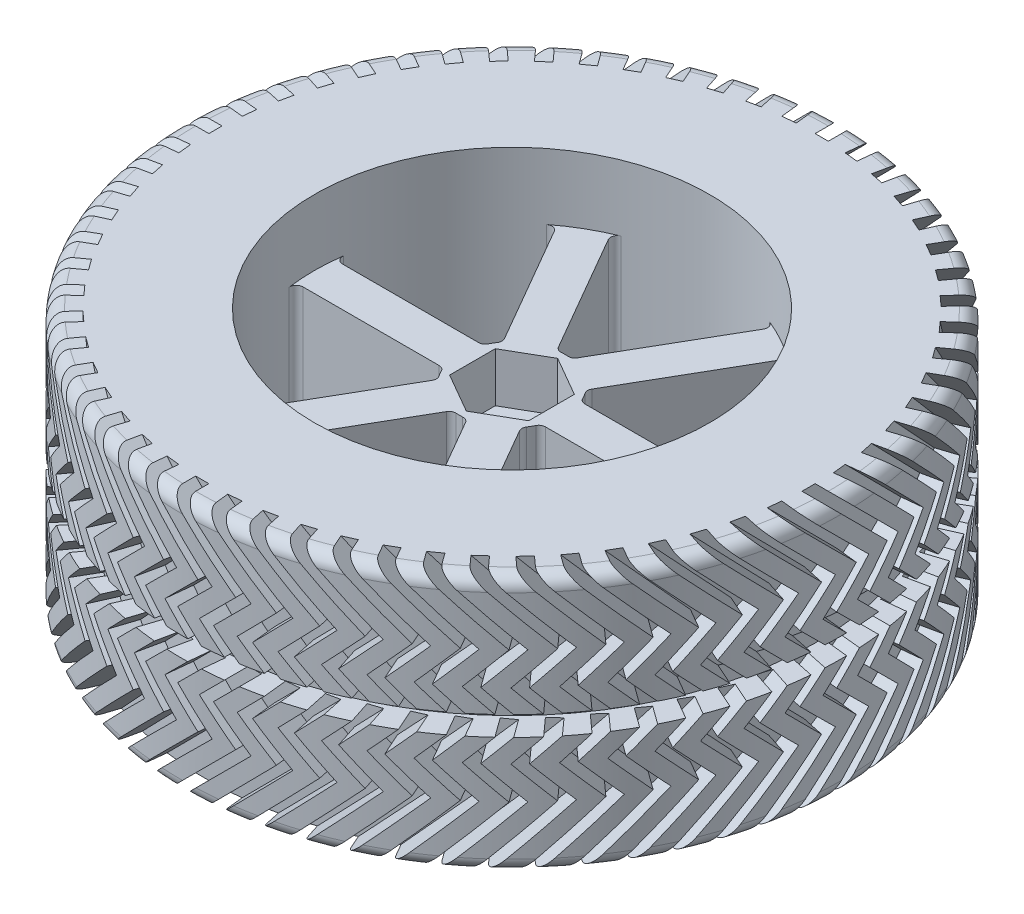
SolidWorks part; units mm, degrees
ref_plane "Front Plane" through (0, 0, 0) normal (0, 0, 1) x (1, 0, 0)
ref_plane "Top Plane" through (0, 0, 0) normal (0, 1, 0) x (1, 0, 0)
ref_plane "Right Plane" through (0, 0, 0) normal (1, 0, 0) x (0, 0, -1)
sketch "Sketch3" plane through (0, 0, 0) normal (0, 1, 0) x (1, 0, 0)
  line L0 (0, 0) -> (-46515.0292, 0) construction
  line L1 (0, 0) -> (0, -46515.0292) construction
  circle A0 centre (0, 0) radius 50
  dimension "D1" = 100
extrude "Boss-Extrude1" add sketch "Sketch3" along normal blind 39
sketch "Sketch4" plane through (0, 0, 0) normal (0, 0, 1) x (1, 0, 0)
  line L0 (0, 0) -> (0, -50000) construction
  line L1 (-50, 19.5) -> (49950, 19.5) construction
  line L2 (-50, 39) -> (-50, 0) construction
  line L3 (-30, 39) -> (-30, 29)
  line L4 (50, 39) -> (-50, 39) construction
  line L5 (-30, 29) -> (0, 29)
  line L6 (-30, 39) -> (0, 39)
  line L7 (0, 39) -> (0, 29)
  line L8 (0, 0) -> (0, 10)
  line L9 (-30, 0) -> (0, 0)
  line L10 (-30, 10) -> (0, 10)
  line L11 (-30, 0) -> (-30, 10)
  point P7 (-50, 19.5)
  dimension "D1" = 20
  dimension "D2" = 10
revolve "Cut-Revolve1" cut sketch "Sketch4" angle 360 about L0
sketch "Sketch5" plane through (0, 29, 0) normal (0, 1, 0) x (1, 0, 0)
  line L0 (0, 0) -> (-50000, 0) construction
  line L1 (0, 0) -> (0, -50000) construction
  line L3 (0, 6.9282) -> (-6, 3.4641)
  line L4 (-6, 3.4641) -> (-6, -3.4641)
  line L5 (-6, -3.4641) -> (0, -6.9282)
  line L6 (0, -6.9282) -> (6, -3.4641)
  line L7 (6, -3.4641) -> (6, 3.4641)
  line L8 (6, 3.4641) -> (0, 6.9282)
  circle A1 centre (0, 0) radius 6 construction
  dimension "D1" = 12
extrude "Cut-Extrude1" cut sketch "Sketch5" against normal blind 7.5
sketch "Sketch6" plane through (0, 29, 0) normal (0, 1, 0) x (1, 0, 0)
  line L0 (0, 0) -> (-50000, 0) construction
  line L1 (0, 0) -> (0, -50000) construction
  line L2 (-28.7228, 3) -> (-8.0623, 3)
  line L5 (-16.9595, 23.3747) -> (-6.6292, 5.4821)
  line L14 (11.7633, 26.3747) -> (1.4331, 8.4821)
  line L16 (-11.7633, 26.3747) -> (-1.4331, 8.4821)
  line L18 (28.7228, 3) -> (8.0623, 3)
  line L20 (16.9595, 23.3747) -> (6.6292, 5.4821)
  line L22 (16.9595, -23.3747) -> (6.6292, -5.4821)
  line L23 (28.7228, -3) -> (8.0623, -3)
  line L24 (-11.7633, -26.3747) -> (-1.4331, -8.4821)
  line L25 (11.7633, -26.3747) -> (1.4331, -8.4821)
  line L26 (-28.7228, -3) -> (-8.0623, -3)
  line L27 (-16.9595, -23.3747) -> (-6.6292, -5.4821)
  arc A0 (-6.6624, 4.4286) -> (-7.1665, 3.5556) centre (0, 0) ccw
  arc A1 (-18.4402, 23.6635) -> (-29.7133, 4.1379) centre (0, 0) ccw
  arc A2 (-6.6292, 5.4821) -> (-6.6624, 4.4286) centre (-7.4952, 4.9821) cw
  arc A3 (-8.0623, 3) -> (-7.1665, 3.5556) centre (-8.0623, 4) ccw
  arc A4 (-28.7228, 3) -> (-29.7133, 4.1379) centre (-28.7228, 4) cw
  arc A5 (-16.9595, 23.3747) -> (-18.4402, 23.6635) centre (-17.8255, 22.8747) ccw
  arc A6 (11.7633, 26.3747) -> (11.2731, 27.8014) centre (10.8973, 26.8747) ccw
  arc A7 (1.4331, 8.4821) -> (0.504, 7.9841) centre (0.567, 8.9821) cw
  arc A8 (0.504, 7.9841) -> (-0.504, 7.9841) centre (0, 0) ccw
  arc A9 (-1.4331, 8.4821) -> (-0.504, 7.9841) centre (-0.567, 8.9821) ccw
  arc A10 (-11.7633, 26.3747) -> (-11.2731, 27.8014) centre (-10.8973, 26.8747) cw
  arc A11 (11.2731, 27.8014) -> (-11.2731, 27.8014) centre (0, 0) ccw
  arc A12 (28.7228, 3) -> (29.7133, 4.1379) centre (28.7228, 4) ccw
  arc A13 (8.0623, 3) -> (7.1665, 3.5556) centre (8.0623, 4) cw
  arc A14 (7.1665, 3.5556) -> (6.6624, 4.4286) centre (0, 0) ccw
  arc A15 (6.6292, 5.4821) -> (6.6624, 4.4286) centre (7.4952, 4.9821) ccw
  arc A16 (16.9595, 23.3747) -> (18.4402, 23.6635) centre (17.8255, 22.8747) cw
  arc A17 (29.7133, 4.1379) -> (18.4402, 23.6635) centre (0, 0) ccw
  arc A18 (16.9595, -23.3747) -> (18.4402, -23.6635) centre (17.8255, -22.8747) ccw
  arc A19 (6.6292, -5.4821) -> (6.6624, -4.4286) centre (7.4952, -4.9821) cw
  arc A20 (6.6624, -4.4286) -> (7.1665, -3.5556) centre (0, 0) ccw
  arc A21 (8.0623, -3) -> (7.1665, -3.5556) centre (8.0623, -4) ccw
  arc A22 (28.7228, -3) -> (29.7133, -4.1379) centre (28.7228, -4) cw
  arc A23 (18.4402, -23.6635) -> (29.7133, -4.1379) centre (0, 0) ccw
  arc A24 (-11.7633, -26.3747) -> (-11.2731, -27.8014) centre (-10.8973, -26.8747) ccw
  arc A25 (-1.4331, -8.4821) -> (-0.504, -7.9841) centre (-0.567, -8.9821) cw
  arc A26 (-0.504, -7.9841) -> (0.504, -7.9841) centre (0, 0) ccw
  arc A27 (1.4331, -8.4821) -> (0.504, -7.9841) centre (0.567, -8.9821) ccw
  arc A28 (11.7633, -26.3747) -> (11.2731, -27.8014) centre (10.8973, -26.8747) cw
  arc A29 (-11.2731, -27.8014) -> (11.2731, -27.8014) centre (0, 0) ccw
  arc A30 (-28.7228, -3) -> (-29.7133, -4.1379) centre (-28.7228, -4) ccw
  arc A31 (-8.0623, -3) -> (-7.1665, -3.5556) centre (-8.0623, -4) cw
  arc A32 (-7.1665, -3.5556) -> (-6.6624, -4.4286) centre (0, 0) ccw
  arc A33 (-6.6292, -5.4821) -> (-6.6624, -4.4286) centre (-7.4952, -4.9821) ccw
  arc A34 (-16.9595, -23.3747) -> (-18.4402, -23.6635) centre (-17.8255, -22.8747) cw
  arc A35 (-29.7133, -4.1379) -> (-18.4402, -23.6635) centre (0, 0) ccw
  point P10 (-6.3062, 4.9226)
  point P20 (-17.5229, 24.3505)
  point P35 (0, 0)
  point P92 (0, 0)
  dimension "D1" = 16
  dimension "D2" = 60
  dimension "D6" = 1
  dimension "D3" = 3
  dimension "D4" = 60
  dimension "D5" = 22.4334
  dimension "D7" = 6
extrude "Cut-Extrude2" cut sketch "Sketch6" against normal through all
sketch "Sketch7" plane through (0, 21.5, 0) normal (0, 1, 0) x (1, 0, 0)
  line L0 (0, 0) -> (-50000, 0) construction
  line L1 (0, 0) -> (0, -50000) construction
  circle A0 centre (0, 0) radius 2
  dimension "D1" = 4
extrude "Cut-Extrude3" cut sketch "Sketch7" against normal through all
fillet "Fillet1" radius 2 2 edges at (0, 0, 50) (0, 39, 50)
sketch "Sketch8" plane through (0, 0, 0) normal (0, 0, 1) x (1, 0, 0)
  line L0 (0, 0) -> (0, 50000) construction
  line L1 (-50, 19.5) -> (49950, 19.5) construction
  line L2 (-50, 37) -> (-50, 2) construction
  line L3 (0, 39) -> (9.5, 29.5)
  line L4 (48, 39) -> (-48, 39) construction
  line L5 (9.5, 29.5) -> (4.5, 24.5)
  line L6 (4.5, 24.5) -> (9.5, 19.5)
  line L7 (4.5, 14.5) -> (9.5, 19.5)
  line L8 (9.5, 9.5) -> (4.5, 14.5)
  line L9 (0, 0) -> (9.5, 9.5)
  line L10 (-2, 39) -> (7.5, 29.5)
  line L11 (7.5, 29.5) -> (2.5, 24.5)
  line L12 (2.5, 24.5) -> (7.5, 19.5)
  line L13 (2.5, 14.5) -> (7.5, 19.5)
  line L14 (7.5, 9.5) -> (2.5, 14.5)
  line L15 (-2, 0) -> (7.5, 9.5)
  line L16 (-2, 39) -> (0, 39)
  line L17 (-2, 0) -> (0, 0)
  point P7 (-50, 19.5)
  dimension "D1" = 45
  dimension "D2" = 5
  dimension "D4" = 2
  dimension "D3" = 2
extrude "Cut-Extrude4" cut sketch "Sketch8" against normal blind 4 from offset 50
pattern_circular "CirPattern1" count 60 over 360 about axis through (0, 39, 0) along (0, 1, 0) of "Cut-Extrude4"
sketch "Sketch9" plane through (0, 0, 0) normal (0, 0, 1) x (1, 0, 0)
  line L0 (0, 0) -> (0, -50000) construction
  line L1 (-49.9475, 19.5) -> (49950.0525, 19.5) construction
  line L3 (-53.9475, 21) -> (-45.9475, 21)
  line L4 (-53.9475, 21) -> (-53.9475, 18)
  line L5 (-53.9475, 18) -> (-45.9475, 18)
  line L6 (-45.9475, 21) -> (-45.9475, 18)
  line L7 (-53.9475, 21) -> (-45.9475, 18) construction
  line L8 (-53.9475, 18) -> (-45.9475, 21) construction
  point P7 (-49.9475, 19.5)
  dimension "D1" = 8
  dimension "D2" = 3
revolve "Cut-Revolve2" cut sketch "Sketch9" angle 360 about L0
